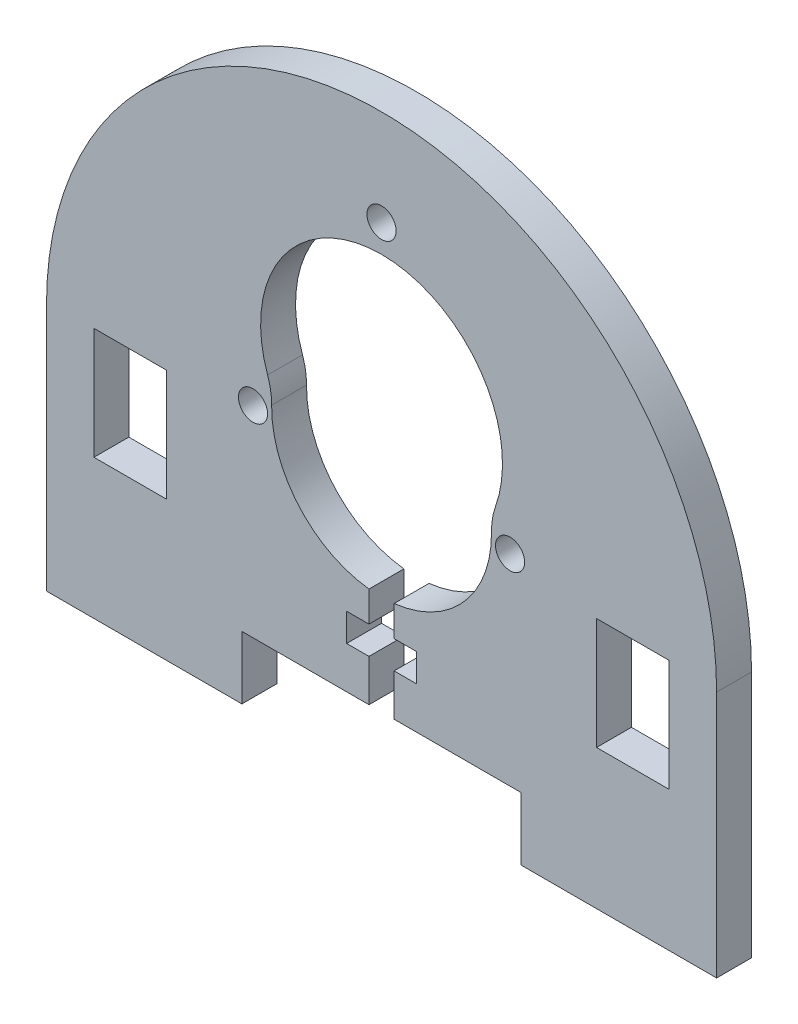
SolidWorks part; units mm, degrees
ref_plane "Front Plane" through (0, 0, 0) normal (0, 0, 1) x (1, 0, 0)
ref_plane "Top Plane" through (0, 0, 0) normal (0, 1, 0) x (1, 0, 0)
ref_plane "Right Plane" through (0, 0, 0) normal (1, 0, 0) x (0, 0, -1)
sketch "Sketch1" plane through (0, 0, 0) normal (0, 0, 1) x (1, 0, 0)
  line L0 (-30.48, 19.5049) -> (30.48, 19.5049) construction
  line L1 (30.48, -11.2601) -> (-30.48, -11.2601)
  line L2 (30.48, -11.2601) -> (30.48, 11.2601)
  line L3 (30.48, 11.2601) -> (-30.48, 11.2601) construction
  line L4 (-30.48, -11.2601) -> (-30.48, 11.2601)
  line L5 (30.48, -11.2601) -> (-30.48, 11.2601) construction
  line L6 (30.48, 11.2601) -> (-30.48, -11.2601) construction
  line L7 (0, 41.7401) -> (0, -11.2601) construction
  arc A0 (-30.48, 11.2601) -> (30.48, 11.2601) centre (0, 11.2601) cw
  circle A3 centre (0, 19.5049) radius 16.5 construction
  circle A4 centre (0, 25.5049) radius 2.5 construction
  point P0 (0, 0)
  dimension "D2" = 33
  dimension "D4" = 5
  dimension "D1" = 30.765
  dimension "D3" = 6
  dimension "D5" = 60.96
  dimension "D6" = 22.2352
extrude "Boss-Extrude1" add sketch "Sketch1" along normal blind 3.175
sketch "Sketch2" plane through (0, 0, 3.175) normal (0, 0, 1) x (1, 0, 0)
  circle A0 centre (0, 19.5049) radius 11
  dimension "D1" = 22
extrude "Cut-Extrude1" cut sketch "Sketch2" against normal up to next
sketch "Sketch3" plane through (0, 0, 3.175) normal (0, 0, 1) x (1, 0, 0)
  line L0 (30.48, -11.2601) -> (-30.48, -11.2601) construction
  line L1 (-12.7, -11.2601) -> (12.7, -11.2601)
  line L2 (-12.7, -11.2601) -> (-12.7, -5.5451)
  line L3 (-12.7, -5.5451) -> (12.7, -5.5451)
  line L4 (12.7, -11.2601) -> (12.7, -5.5451)
  line L6 (0, 41.7401) -> (0, -11.2601) construction
  point P6 (0, -5.5451)
  dimension "D1" = 5.715
  dimension "D2" = 25.4
extrude "Cut-Extrude2" cut sketch "Sketch3" against normal up to next
sketch "Sketch4" plane through (0, 0, 3.175) normal (0, 0, 1) x (1, 0, 0)
  line L0 (-30.48, -11.2601) -> (-12.7, -11.2601) construction
  line L1 (30.48, -11.2601) -> (-30.48, -11.2601) construction
  line L2 (-12.7, -5.5451) -> (-12.7, -11.2601) construction
  line L3 (-22.8266, -1014.3325) -> (-22.8266, 48985.6675) construction
  line L4 (0, -1.7463) -> (0, 1.7463) construction
  line L5 (-21.2391, 3.9799) -> (-24.4141, 3.9799)
  line L6 (-21.2391, 3.9799) -> (-21.2391, 10.3299)
  line L7 (-21.2391, 10.3299) -> (-24.4141, 10.3299)
  line L8 (-24.4141, 3.9799) -> (-24.4141, 10.3299)
  line L9 (-21.2391, 3.9799) -> (-24.4141, 10.3299) construction
  line L10 (-21.2391, 10.3299) -> (-24.4141, 3.9799) construction
  line L11 (21.2391, 1.4399) -> (24.4141, -4.9101) construction
  line L12 (-21.2391, -4.9101) -> (-24.4141, -4.9101)
  line L13 (-21.2391, -4.9101) -> (-21.2391, 1.4399)
  line L14 (-21.2391, 1.4399) -> (-24.4141, 1.4399)
  line L15 (-24.4141, -4.9101) -> (-24.4141, 1.4399)
  line L16 (-21.2391, -4.9101) -> (-24.4141, 1.4399) construction
  line L17 (-21.2391, 1.4399) -> (-24.4141, -4.9101) construction
  line L18 (21.2391, -4.9101) -> (24.4141, 1.4399) construction
  line L19 (21.2391, 10.3299) -> (24.4141, 3.9799) construction
  line L20 (21.2391, 3.9799) -> (24.4141, 10.3299) construction
  line L21 (24.4141, -4.9101) -> (24.4141, 1.4399)
  line L22 (21.2391, 1.4399) -> (24.4141, 1.4399)
  line L23 (21.2391, -4.9101) -> (21.2391, 1.4399)
  line L24 (21.2391, -4.9101) -> (24.4141, -4.9101)
  line L25 (24.4141, 3.9799) -> (24.4141, 10.3299)
  line L26 (21.2391, 10.3299) -> (24.4141, 10.3299)
  line L27 (21.2391, 3.9799) -> (21.2391, 10.3299)
  line L28 (21.2391, 3.9799) -> (24.4141, 3.9799)
  point P7 (-22.8266, -11.2601)
  point P9 (-22.8266, 7.1549)
  point P17 (-22.8266, -1.7351)
  point P23 (-21.59, -11.2601)
  point P35 (22.8266, -1.7351)
  point P36 (22.8266, 7.1549)
  dimension "D1" = 6.35
  dimension "D2" = 6.35
  dimension "D3" = 3.175
  dimension "D4" = 3.175
  dimension "D5" = 6.35
  dimension "D6" = 2.54
  dimension "D7" = 1.2366
extrude "Cut-Extrude3" [suppressed] cut sketch "Sketch4" against normal up to next
sketch "Sketch5" plane through (0, 0, 3.175) normal (0, 0, 1) x (1, 0, 0)
  line L0 (0, 41.7401) -> (0, -11.2601) construction
  line L1 (3.175, -1.7351) -> (1.143, -1.7351)
  line L2 (3.175, -1.7351) -> (3.175, 0.8049)
  line L3 (3.175, 0.8049) -> (1.143, 0.8049)
  line L4 (-3.175, -1.7351) -> (-3.175, 0.8049)
  line L5 (3.175, -1.7351) -> (-3.175, 0.8049) construction
  line L6 (3.175, 0.8049) -> (-3.175, -1.7351) construction
  line L7 (12.7, -5.5451) -> (-12.7, -5.5451) construction
  line L8 (-1.143, 0.8049) -> (-3.175, 0.8049)
  line L9 (-1.143, -5.5451) -> (1.143, -5.5451)
  line L10 (-1.143, -5.5451) -> (-1.143, -1.7351)
  line L11 (-1.143, 9.6949) -> (1.143, 9.6949)
  line L12 (1.143, -5.5451) -> (1.143, -1.7351)
  line L13 (-1.143, 0.8049) -> (-1.143, 9.6949)
  line L14 (1.143, 0.8049) -> (1.143, 9.6949)
  line L15 (-1.143, -1.7351) -> (-3.175, -1.7351)
  point P0 (0, -0.4651)
  point P14 (0, 9.6949)
  dimension "D1" = 6.35
  dimension "D2" = 2.54
  dimension "D3" = 3.81
  dimension "D4" = 2.286
  dimension "D5" = 15.24
extrude "Cut-Extrude4" cut sketch "Sketch5" against normal up to next
sketch "Sketch6" plane through (0, 0, 0) normal (0, 0, 1) x (1, 0, 0)
  line L0 (0, 41.7401) -> (0, -11.2601) construction
  circle A0 centre (0, 33.0049) radius 1.325
  circle A1 centre (11.6913, 12.7549) radius 1.325
  circle A2 centre (-11.6913, 12.7549) radius 1.325
  point P10 (0, 19.5049)
  dimension "D1" = 2.65
  dimension "D3" = 13.5
  dimension "D2" = 3
extrude "Cut-Extrude6" cut sketch "Sketch6" along normal through all
sketch "Sketch7" plane through (0, 0, 0) normal (0, 0, 1) x (1, 0, 0)
  line L0 (0, 41.7401) -> (0, -11.2601) construction
  circle A0 centre (0, 13.5049) radius 10
  dimension "D1" = 20
  dimension "D2" = 6
extrude "Cut-Extrude7" cut sketch "Sketch7" along normal through all
fillet "Fillet1" radius 6.35 2 edges at (-9.9216, 14.7549, 1.5875) (9.9216, 14.7549, 1.5875)
sketch "Sketch8" plane through (0, 0, 3.175) normal (0, 0, 1) x (1, 0, 0)
  line L0 (-22.86, 31.4207) -> (-22.86, -11.2601) construction
  line L1 (30.48, -11.2601) -> (-30.48, -11.2601) construction
  line L2 (-30.48, -11.2601) -> (-30.48, 11.2601) construction
  line L3 (0, -1.7463) -> (0, 1.7463) construction
  line L4 (22.86, 31.4207) -> (22.86, -11.2601) construction
  line L5 (19.558, 11.5999) -> (19.558, 1.4399)
  line L6 (-26.162, 11.5999) -> (-19.558, 11.5999)
  line L7 (-26.162, 11.5999) -> (-26.162, 1.4399)
  line L8 (-26.162, 1.4399) -> (-19.558, 1.4399)
  line L9 (-19.558, 11.5999) -> (-19.558, 1.4399)
  line L10 (26.162, 1.4399) -> (19.558, 1.4399)
  line L11 (26.162, 11.5999) -> (26.162, 1.4399)
  line L12 (26.162, 11.5999) -> (19.558, 11.5999)
  arc A0 (30.48, 11.2601) -> (-30.48, 11.2601) centre (0, 11.2601) ccw construction
  point P17 (-22.86, 11.5999)
  dimension "D1" = 7.62
  dimension "D2" = 6.604
  dimension "D3" = 22.86
  dimension "D4" = 10.16
extrude "Cut-Extrude8" cut sketch "Sketch8" against normal up to next
equation "\"D2@Sketch1\"=33mm"
equation "\"D1@Sketch1\"=0.75+\"thickness0.25\"+\"motor offset\""
equation "\"t\"=0.125"
equation "\"D1@Boss-Extrude1\"=\"t\""
equation "\"D4@Sketch4\"=\"t\""
equation "\"D3@Sketch4\"=\"t\""
equation "\"motor offset\"= 6mm"
equation "\"thickness0.25\"= 0.225in"
equation "\"thickness0.125\"= 0.122in"
equation "\"motor diameter\"= 33mm"
equation "\"D3@Sketch1\"=\"motor offset\""
equation "\"D1@Sketch3\"=\"thickness0.25\""
equation "\"D2@Sketch7\"=\"motor offset\""
